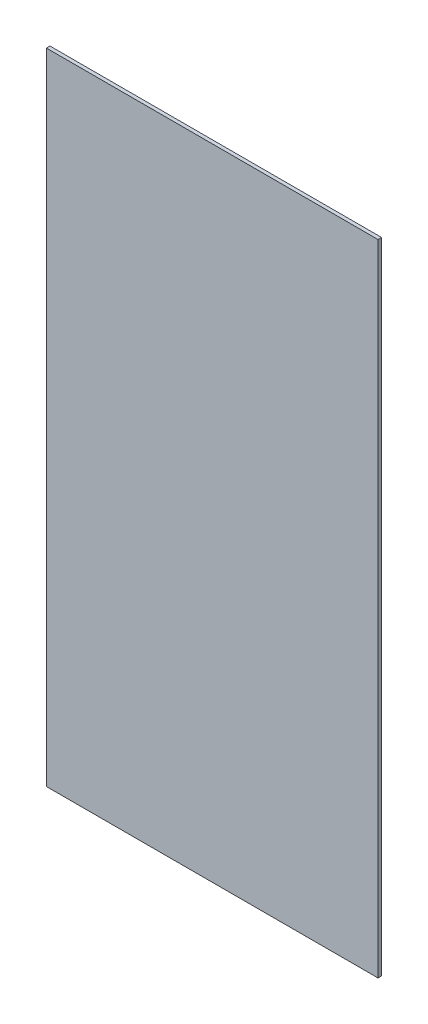
SolidWorks part; units mm, degrees
ref_plane "Plan de face" through (0, 0, 0) normal (0, 0, 1) x (1, 0, 0)
ref_plane "Plan de dessus" through (0, 0, 0) normal (0, 1, 0) x (1, 0, 0)
ref_plane "Plan de droite" through (0, 0, 0) normal (1, 0, 0) x (0, 0, -1)
sketch "Esquisse1" plane through (0, 0, 0) normal (0, 0, 1) x (1, 0, 0)
  line L0 (202.5709, -453.2994) -> (202.5709, 86.7006)
  line L1 (-77.4291, 86.7006) -> (202.5709, 86.7006)
  line L2 (-77.4291, 86.7006) -> (-77.4291, -453.2994)
  line L3 (-77.4291, -453.2994) -> (202.5709, -453.2994)
  dimension "D1" = 280
  dimension "D2" = 540
extrude "Boss.-Extru.1" add sketch "Esquisse1" along normal blind 3
equation "\"EpaisseurPlaque\"= 3"
equation "\"D1@Boss.-Extru.1\"=\"EpaisseurPlaque\""
equation "\"ProfondeurBoite\"=460"
equation "\"LongueurSyphon\"=170"
equation "\"LargeurSyphon\"=120"
equation "\"HauteurCoteDroit\"= 490"
equation "\"HauteurCoteGauche\"= 540"
equation "\"HauteurSolSyphon\"= 300"
equation "\"HauteurSyphon\"=\"HauteurCoteGauche\"-\"HauteurSolSyphon\""
equation "\"D2@Esquisse1\"= \"HauteurCoteGauche\""
equation "\"LargeurBoite\"= \"LargeurDroite\" + \"LargeurGauche\" + \"LargeurSyphon\""
equation "\"D1@Esquisse1\"= \"LargeurBoite\""
equation "\"LargeurDroite\"=10"
equation "\"LargeurGauche\"=150"
